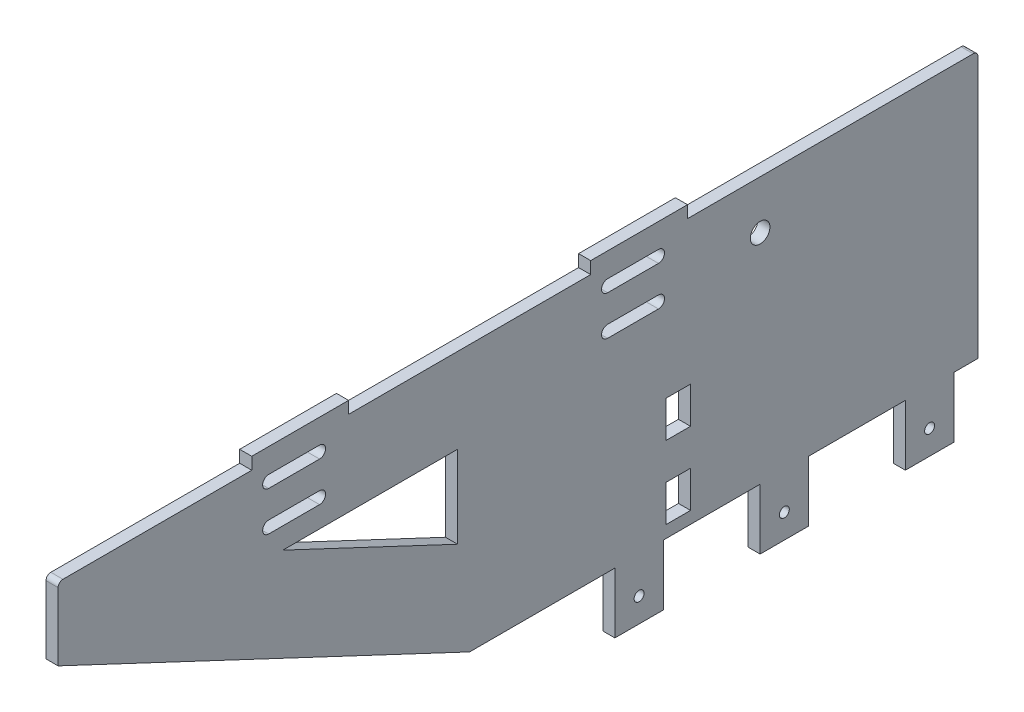
SolidWorks part; units mm, degrees
ref_plane "前基準面" through (0, 0, 0) normal (0, 0, 1) x (1, 0, 0)
ref_plane "上基準面" through (0, 0, 0) normal (0, 1, 0) x (1, 0, 0)
ref_plane "右基準面" through (0, 0, 0) normal (1, 0, 0) x (0, 0, -1)
sketch "草圖1" plane through (0, 0, 0) normal (1, 0, 0) x (0, 0, -1)
  line L1 (90, 55) -> (-90, 55)
  line L2 (90, 55) -> (90, -55)
  line L3 (90, -55) -> (-90, -55)
  line L4 (-90, 55) -> (-90, -55)
  line L5 (0, -55) -> (0, 55) construction
  line L6 (90, 0) -> (-90, 0) construction
  circle A0 centre (0, 35) radius 4.05
  point P0 (0, 0)
  dimension "D3" = 8.1
  dimension "D1" = 180
  dimension "D2" = 110
  dimension "D4" = 90
  dimension "D5" = 90
extrude "填料-伸長1" add sketch "草圖1" along normal blind 5
sketch "草圖2" plane through (5, 0, 0) normal (1, 0, 0) x (0, 0, -1)
  line L0 (-90, -55) -> (90, -55) construction
  line L1 (-60, -55) -> (-40, -55)
  line L4 (-60, -55) -> (-60, -80)
  line L5 (-60, -80) -> (-40, -80)
  line L6 (-40, -80) -> (-40, -55)
  line L8 (0, -55) -> (0, -80)
  line L9 (0, -80) -> (20, -80)
  line L10 (20, -80) -> (20, -55)
  line L12 (60, -55) -> (60, -80)
  line L13 (60, -80) -> (80, -80)
  line L14 (80, -80) -> (80, -55)
  line L17 (-90, 55) -> (-90, -55) construction
  line L18 (-70, -70) -> (90, -70) construction
  line L19 (0, -55) -> (20, -55)
  line L20 (60, -55) -> (80, -55)
  line L21 (-60, -60) -> (80, -60) construction
  circle A0 centre (-50, -70) radius 2.05
  circle A1 centre (10, -70) radius 2.05
  circle A2 centre (70, -70) radius 2.05
  point P27 (-50, -80)
  point P30 (70, -80)
  point P32 (10, -55)
  dimension "D7" = 4.1
  dimension "D1" = 25
  dimension "D2" = 30
  dimension "D3" = 40
  dimension "D4" = 40
  dimension "D5" = 20
  dimension "D6" = 5
  dimension "D8" = 10
extrude "填料-伸長2" add sketch "草圖2" against normal blind 5
sketch "草圖3" plane through (5, 0, 0) normal (1, 0, 0) x (0, 0, -1)
  line L0 (-90, -55) -> (90, -55) construction
  line L1 (-90, 55) -> (-90, -55) construction
  line L2 (90, -55) -> (90, 55) construction
  line L4 (-90, 55) -> (-290, 55)
  line L5 (-290, 55) -> (-290, 25)
  line L6 (-290, 25) -> (-120, -55)
  line L7 (-120, -55) -> (-90, -55)
  line L8 (-90, 55) -> (-90, -55)
  line L9 (-125, 20) -> (-125, -13.9653)
  line L10 (-125, -13.9653) -> (-125, -13.9653)
  line L11 (-197.1762, 20) -> (-125, -13.9653)
  line L12 (-197.1762, 20) -> (-197.1762, 20)
  line L13 (-125, 20) -> (-197.1762, 20)
  line L14 (-90, -55) -> (-60, -55) construction
  point P18 (0, 0)
  point P19 (0, 0)
  dimension "D2" = 30
  dimension "D3" = 30
  dimension "D4" = 200
  dimension "D5" = 35
extrude "填料-伸長3" add sketch "草圖3" against normal blind 5
sketch "草圖4" plane through (5, 0, 0) normal (1, 0, 0) x (0, 0, -1)
  line L1 (-38.85, -4.8) -> (-28.75, -4.8)
  line L2 (-38.85, -4.8) -> (-38.85, -19.9)
  line L3 (-38.85, -19.9) -> (-28.75, -19.9)
  line L4 (-28.75, -4.8) -> (-28.75, -19.9)
  line L5 (-38.85, -34.9) -> (-28.75, -34.9)
  line L6 (-38.85, -34.9) -> (-38.85, -50)
  line L7 (-38.85, -50) -> (-28.75, -50)
  line L8 (-28.75, -34.9) -> (-28.75, -50)
  line L10 (-120, -55) -> (-60, -55) construction
  dimension "D1" = 81.15
  dimension "D3" = 10.1
  dimension "D4" = 15
  dimension "D5" = 15.1
  dimension "D6" = 5
extrude "除料-伸長1" cut sketch "草圖4" against normal through all
sketch "草圖5" plane through (0, 55, 0) normal (0, 1, 0) x (1, 0, 0)
  line L0 (0, -120) -> (5, -120) construction
  line L1 (0, -120) -> (5, -120) construction
  line L2 (0, 90) -> (0, -290) construction
  line L3 (0, -30) -> (5, -30)
  line L4 (0, -30) -> (0, -70)
  line L5 (0, -70) -> (5, -70)
  line L6 (5, -30) -> (5, -70)
  line L7 (5, 90) -> (5, -290) construction
  line L9 (0, -170) -> (5, -170)
  line L10 (0, -170) -> (0, -210)
  line L11 (0, -210) -> (5, -210)
  line L12 (5, -170) -> (5, -210)
  dimension "D1" = 50
  dimension "D2" = 100
  dimension "D3" = 40
extrude "填料-伸長4" add sketch "草圖5" along normal blind 5
sketch "草圖6" plane through (5, 0, 0) normal (1, 0, 0) x (0, 0, -1)
  line L0 (-63, 47.5) -> (-42, 47.5) construction
  line L1 (-63, 50) -> (-42, 50)
  line L2 (-63, 45) -> (-42, 45)
  line L3 (-63, 31.2) -> (-42, 31.2) construction
  line L4 (-63, 33.7) -> (-42, 33.7)
  line L5 (-63, 28.7) -> (-42, 28.7)
  line L6 (90, 55) -> (-30, 55) construction
  line L7 (-70, 55) -> (-35, 55) construction
  line L8 (-70, 55) -> (-70, 20) construction
  line L9 (-70, 20) -> (-35, 20) construction
  line L10 (-35, 55) -> (-35, 20) construction
  line L11 (-203, 47.5) -> (-182, 47.5) construction
  line L12 (-203, 50) -> (-182, 50)
  line L13 (-203, 45) -> (-182, 45)
  line L14 (-203, 31.2) -> (-182, 31.2) construction
  line L15 (-203, 33.7) -> (-182, 33.7)
  line L16 (-203, 28.7) -> (-182, 28.7)
  arc A0 (-63, 50) -> (-63, 45) centre (-63, 47.5) ccw
  arc A1 (-42, 45) -> (-42, 50) centre (-42, 47.5) ccw
  arc A2 (-63, 33.7) -> (-63, 28.7) centre (-63, 31.2) ccw
  arc A3 (-42, 28.7) -> (-42, 33.7) centre (-42, 31.2) ccw
  arc A4 (-63, 50) -> (-63, 45) centre (-63, 47.5) cw construction
  arc A5 (-42, 50) -> (-42, 45) centre (-42, 47.5) ccw construction
  arc A6 (-203, 50) -> (-203, 45) centre (-203, 47.5) ccw
  arc A7 (-182, 45) -> (-182, 50) centre (-182, 47.5) ccw
  arc A8 (-203, 33.7) -> (-203, 28.7) centre (-203, 31.2) ccw
  arc A9 (-182, 28.7) -> (-182, 33.7) centre (-182, 31.2) ccw
  point P2 (-52.5, 47.5)
  point P7 (-52.5, 31.2)
  point P16 (-60.5, 47.5)
  point P19 (-44.5, 47.5)
  point P21 (-52.5, 55)
  point P30 (-192.5, 47.5)
  point P36 (-192.5, 31.2)
  dimension "D1" = 5
  dimension "D2" = 16
  dimension "D3" = 11.3
  dimension "D4" = 35
  dimension "D5" = 5
  dimension "D6" = 35
  dimension "D7" = 50
  dimension "D9" = 140
  dimension "D8" = 2
extrude "除料-伸長2" cut sketch "草圖6" against normal through all
fillet "圓角1" radius 2 2 edges at (2.5, 55, -90) (2.5, 55, 290)
